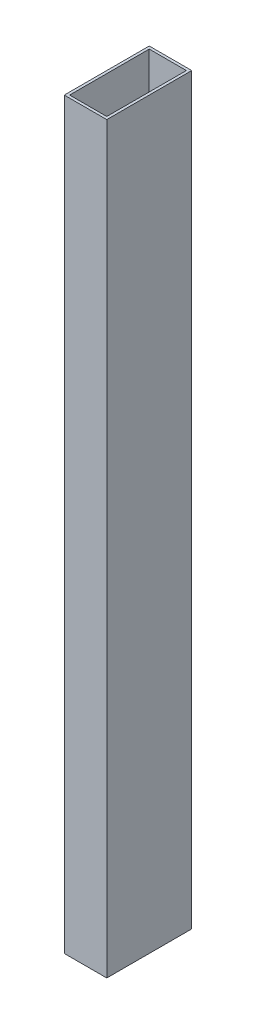
SolidWorks part; units mm, degrees
material "6061-T6 (SS)"
ref_plane "Front" through (0, 0, 0) normal (0, 0, 1) x (1, 0, 0)
ref_plane "Top" through (0, 0, 0) normal (0, 1, 0) x (1, 0, 0)
ref_plane "Right" through (0, 0, 0) normal (1, 0, 0) x (0, 0, -1)
sketch "Sketch1" plane through (0, 0, 0) normal (0, 1, 0) x (1, 0, 0)
  line L1 (12.7, 25.4) -> (-12.7, 25.4)
  line L2 (12.7, 25.4) -> (12.7, -25.4)
  line L3 (12.7, -25.4) -> (-12.7, -25.4)
  line L4 (-12.7, 25.4) -> (-12.7, -25.4)
  line L5 (12.7, 25.4) -> (-12.7, -25.4) construction
  line L6 (12.7, -25.4) -> (-12.7, 25.4) construction
  point P0 (0, 0)
  dimension "D1" = 25.4
  dimension "D2" = 50.8
extrude "Extrude-Thin1" add sketch "Sketch1" along normal up to surface (444.5 mm away) thin thin type one direction reverse wall 1.5875
